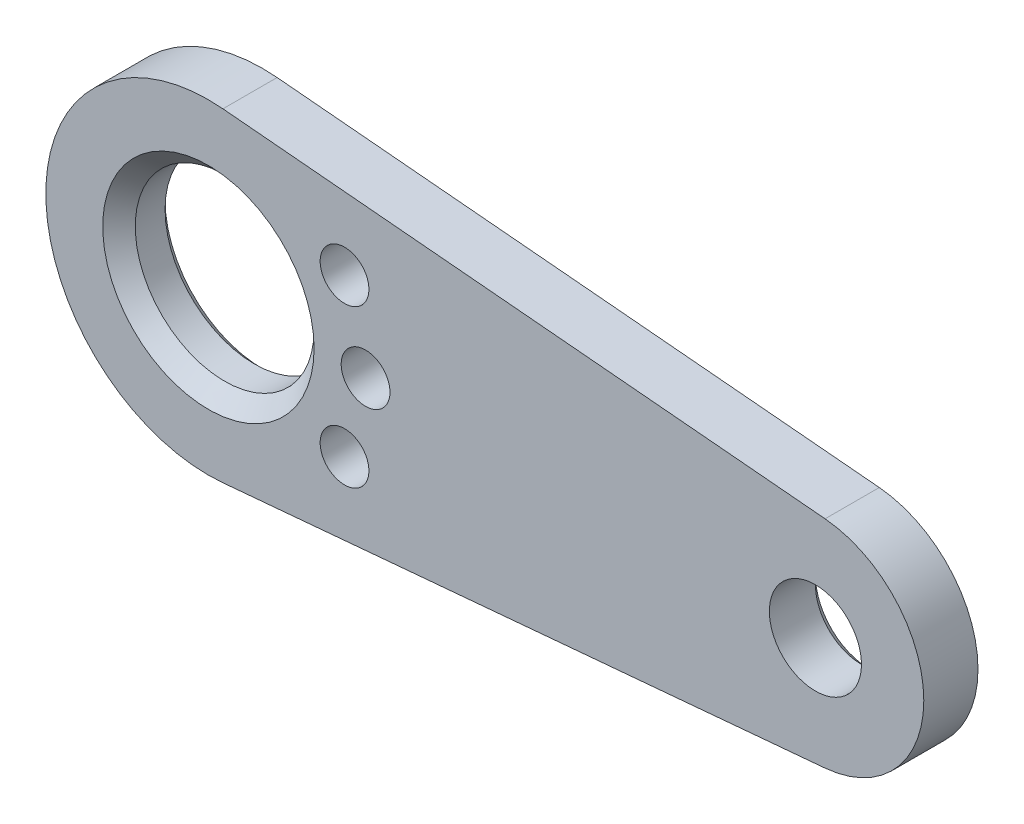
SolidWorks part; units mm, degrees
ref_plane "Front Plane" through (0, 0, 0) normal (0, 0, 1) x (1, 0, 0)
ref_plane "Top Plane" through (0, 0, 0) normal (0, 1, 0) x (1, 0, 0)
ref_plane "Right Plane" through (0, 0, 0) normal (1, 0, 0) x (0, 0, -1)
sketch "Sketch1" plane through (0, 0, 0) normal (0, 0, 1) x (1, 0, 0)
  line L0 (0.2679, 2.988) -> (11.3786, 1.992)
  line L1 (0, 0) -> (11.2, 0) construction
  line L2 (0.2679, -2.988) -> (11.3786, -1.992)
  arc A0 (0.2679, 2.988) -> (0.2679, -2.988) centre (0, 0) ccw
  arc A1 (11.3786, -1.992) -> (11.3786, 1.992) centre (11.2, 0) ccw
  dimension "D1" = 3
  dimension "D2" = 2
  dimension "D3" = 11.2
extrude "Boss-Extrude1" add sketch "Sketch1" against normal blind 1
sketch "Sketch2" plane through (0, 0, 0) normal (0, 0, 1) x (1, 0, 0)
  circle A0 centre (0, 0) radius 1.65
  circle A1 centre (11.2, 0) radius 0.85
  dimension "D1" = 3.3
  dimension "D2" = 1.7
extrude "Cut-Extrude1" cut sketch "Sketch2" against normal through all
chamfer "Chamfer1" distance 0.3 angle 45 1 edges at (1.65, 0, 0)
chamfer "Chamfer2" distance 0.15 angle 45 2 edges at (1.65, 0, -1) (12.05, 0, -1)
hole_wizard "Ø0.9 (0.9) Diameter Hole1" positions "Sketch4" profile "Sketch3" hole size "Ø0.9" standard "DIN" end condition up to next
sketch "Sketch4" plane through (0, 0, 0) normal (0, 0, 1) x (1, 0, 0)
  line L0 (0, 0) -> (2.9, 0) construction
  line L1 (0, 0) -> (2.5115, 1.45) construction
  line L2 (0, 0) -> (2.5115, -1.45) construction
  circle A0 centre (0, 0) radius 2.9 construction
  point P6 (2.9, 0)
  point P8 (2.5115, 1.45)
  point P10 (2.5115, -1.45)
  dimension "D1" = 5.8
  dimension "D2" = 30
  dimension "D3" = 30
sketch "Sketch3" plane through (2.9, 0, 0) normal (1, 0, 0) x (0, -1, 0)
  line L0 (0, 0) -> (0, 1)
  line L1 (0, 1) -> (0.45, 1)
  line L2 (0.45, 1) -> (0.45, 0)
  line L5 (0.45, 0) -> (0, 0)
  line L11 (0, -6.35) -> (0, 107.95) construction
  dimension "Thru Hole Dia." = 0.9
  dimension "Thru Hole Depth" = 1
